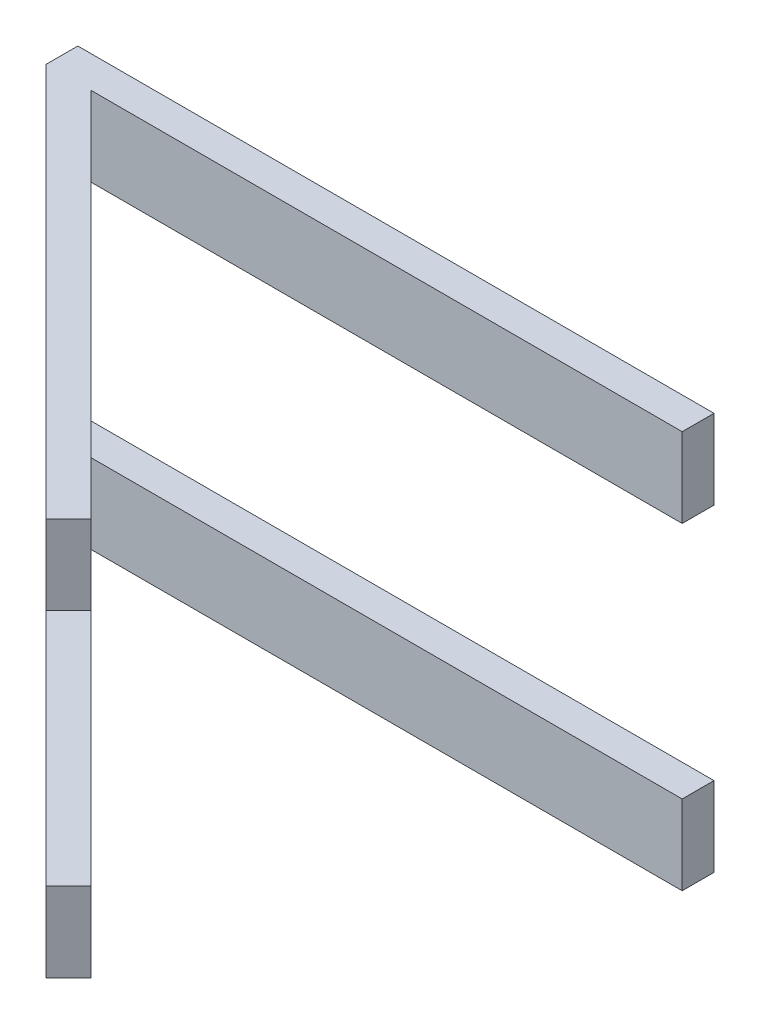
SolidWorks part; units mm, degrees
ref_plane "Alzado" through (0, 0, 0) normal (0, 0, 1) x (1, 0, 0)
ref_plane "Planta" through (0, 0, 0) normal (0, 1, 0) x (1, 0, 0)
ref_plane "Vista lateral" through (0, 0, 0) normal (1, 0, 0) x (0, 0, -1)
sketch "Croquis1" plane through (0, 0, 0) normal (0, 0, 1) x (1, 0, 0)
  line L0 (-50, 25) -> (40, 25) construction
  line L1 (-40, 10) -> (40, 10)
  line L2 (-40, 10) -> (-40, 0)
  line L3 (-40, 0) -> (40, 0)
  line L4 (40, 10) -> (40, 0)
  line L5 (40, 40) -> (40, 50)
  line L6 (-40, 50) -> (40, 50)
  line L7 (-40, 40) -> (-40, 50)
  line L8 (-40, 40) -> (40, 40)
  line L9 (-40, 5) -> (40, 5) construction
  line L10 (-40, 45) -> (40, 45) construction
  dimension "D1" = 10
  dimension "D2" = 15
  dimension "9" = 80
extrude "Saliente-Extruir1" add sketch "Croquis1" along normal blind 4 contours L7 L8 L5 L6 | L1 L4 L3 L2 region at (0, 45, 0)
sketch "Croquis2" plane through (0, 0, 0) normal (0, -1, 0) x (1, 0, 0)
  line L0 (-40, 4) -> (9.4975, 53.4975)
  line L1 (9.4975, 53.4975) -> (12.3259, 50.669)
  line L2 (12.3259, 50.669) -> (-34.3431, 4)
  line L3 (-40, 4) -> (40, 4) construction
  line L4 (-40, 4) -> (-34.3431, 4)
  dimension "D1" = 45
  dimension "D2" = 4
  dimension "D3" = 70
extrude "Saliente-Extruir2" add sketch "Croquis2" against normal up to surface (10 mm away) up to face at (0, 10, 2)
sketch "Croquis3" plane through (0, 50, 0) normal (0, 1, 0) x (1, 0, 0)
  line L0 (-40, -4) -> (9.4975, -53.4975)
  line L1 (9.4975, -53.4975) -> (12.3259, -50.669)
  line L2 (12.3259, -50.669) -> (-34.3431, -4)
  line L3 (-34.3431, -4) -> (-40, -4)
extrude "Saliente-Extruir3" add sketch "Croquis3" against normal up to surface (10 mm away) up to face at (0, 40, 2)
